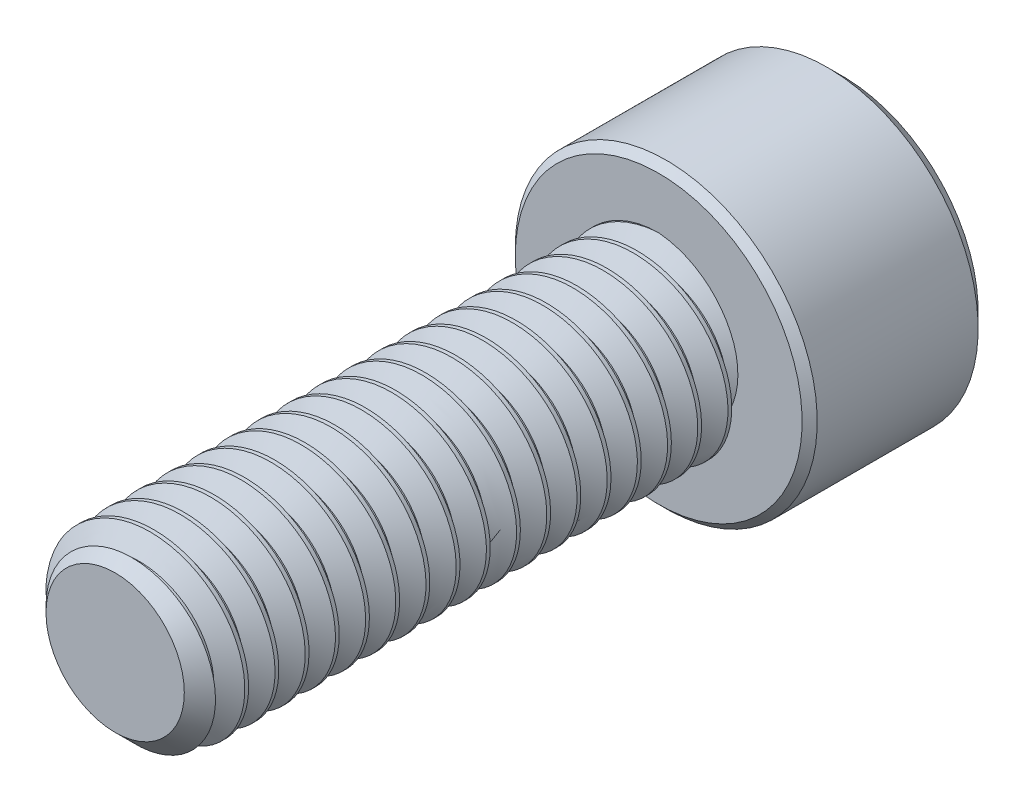
SolidWorks part; units mm, degrees
ref_plane "Front Plane" through (0, 0, 0) normal (0, 0, 1) x (1, 0, 0)
ref_plane "Top Plane" through (0, 0, 0) normal (0, 1, 0) x (1, 0, 0)
ref_plane "Right Plane" through (0, 0, 0) normal (1, 0, 0) x (0, 0, -1)
sketch "Sketch0" plane through (0, 0, 0) normal (1, 0, 0) x (0, 0, -1)
  line L0 (0, 0) -> (14.2875, 0) construction
  point P2 (19.1135, 0)
  point P4 (0, 0)
  dimension "D1" = 14.2875
  dimension "D2" = 4.826
  dimension "Min Thread" = 0
sketch "Sketch1" plane through (0, 0, 0) normal (0, 0, 1) x (1, 0, 0)
  circle A0 centre (0, 0) radius 2.413
  dimension "OD" = 4.826
extrude "Extrude1" add sketch "Sketch1" against normal blind 14.2875
sketch "Sketch2" plane through (0, 0, 0) normal (0, 0, 1) x (1, 0, 0)
  circle A0 centre (0, 0) radius 2.413 construction
  circle A1 centre (0, 0) radius 2.413
curve "Helix/Spiral1" pitch 0.7937 height 15.0812 turns 19 parameters "pitch"=0.7937
chamfer "Chamfer3" distance 0.5953 angle 45 1 edges at (2.413, 0, 0)
sketch "Sketch3" plane through (0, 0, 0) normal (1, 0, 0) x (0, 0, -1)
  line L0 (-0.6945, 2.413) -> (-0.3969, 1.8974)
  line L1 (-0.3969, 1.8974) -> (-0.2977, 1.8974)
  line L2 (-0.2977, 1.8974) -> (0, 2.413)
  line L3 (-0.6945, 2.413) -> (0, 2.413)
  line L4 (-0.3473, 2.413) -> (-0.3473, 1.8974) construction
  line L5 (-0.5457, 2.1552) -> (-0.1488, 2.1552) construction
  line L6 (0, 2.413) -> (0, -2.413) construction
  dimension "D1" = 0.0992
  dimension "D2" = 0.3969
  dimension "D3" = 60
sweep "Cut-Sweep1" cut profiles "Sketch3" path "Helix/Spiral1"
sketch "Sketch5" plane through (0, 0, 0) normal (1, 0, 0) x (0, 0, -1)
  line L0 (14.2875, -1.9083) -> (14.2875, 1.7217) construction
  line L1 (14.2875, 2.413) -> (0, 2.413)
  line L2 (14.2875, 2.413) -> (14.2875, 0)
  line L3 (14.2875, 0) -> (-0.8783, 0)
  line L4 (0, 0) -> (14.2875, 0) construction
  line L5 (0, 2.413) -> (-0.8783, 0)
  line L6 (0, 0) -> (16.8275, 0) construction
  dimension "D1" = 70
  dimension "D3" = 2.54
revolve "partially thread" [suppressed] add sketch "Sketch5" angle 360 about L6
sketch "Sketch6" plane through (0, 0, -14.2875) normal (0, 0, -1) x (-1, 0, 0)
  circle A0 centre (0, 0) radius 3.9688
  dimension "head dia" = 7.9375
extrude "Extrude2" add sketch "Sketch6" along normal blind 4.826
sketch "Sketch7" plane through (0, 0, -19.1135) normal (0, 0, -1) x (-1, 0, 0)
  line L1 (0, 2.2914) -> (-1.9844, 1.1457)
  line L2 (-1.9844, 1.1457) -> (-1.9844, -1.1457)
  line L3 (-1.9844, -1.1457) -> (0, -2.2914)
  line L4 (0, -2.2914) -> (1.9844, -1.1457)
  line L5 (1.9844, -1.1457) -> (1.9844, 1.1457)
  line L6 (1.9844, 1.1457) -> (0, 2.2914)
  circle A0 centre (0, 0) radius 1.9844 construction
  dimension "hex dia" = 3.9688
extrude "Cut-Extrude1" cut sketch "Sketch7" against normal blind 2.9766
sketch "Sketch8" plane through (0, 0, -19.1135) normal (0, 0, -1) x (-1, 0, 0)
  circle A0 centre (0, 0) radius 2.2914
extrude "Cut-Extrude2" cut sketch "Sketch8" against normal through all draft 45
chamfer "Chamfer1" distance 0.3969 angle 45 1 edges at (-3.9688, 0, -19.1135)
chamfer "Chamfer2" distance 0.1984 angle 45 1 edges at (-3.9688, 0, -14.2875)
sketch "Sketch9" plane through (0, 0, 0) normal (1, 0, 0) x (0, 0, -1)
  line L0 (0, 2.413) -> (0, -2.413) construction
  line L1 (1.9844, 2.413) -> (1.9844, -2.413) construction
  line L2 (19.1135, 3.9688) -> (19.1135, -3.9688) construction
  line L3 (14.2875, 3.9688) -> (14.2875, -3.9688) construction
  line L4 (14.2875, 3.7703) -> (14.2875, -3.7703) construction
  line L5 (19.1135, -3.5719) -> (19.1135, 3.5719) construction
  line L6 (14.2875, -3.9688) -> (14.2875, 3.9688) construction
  line L7 (0, 1.8177) -> (0, -1.8177) construction
  line L8 (-0.6945, 2.413) -> (0, 2.413) construction
  line L9 (1.9844, 0) -> (0, 0) construction
  dimension "D1" = 1.9844
equation "\"D3@Helix/Spiral1\" = \"screw length@Extrude1\"+\"pitch@Helix/Spiral1\""
equation "\"D1@Sketch3\" = \"pitch@Helix/Spiral1\"*.125"
equation "\"D2@Sketch3\" = \"pitch@Helix/Spiral1\"*.5"
equation "\"D1@Cut-Extrude1\" = \"hex dia@Sketch7\"*.75"
equation "\"D1@Chamfer1\" = \"head dia@Sketch6\"*.05"
equation "\"D1@Sketch9\" = \"pitch@Helix/Spiral1\"*2.50"
equation "\"D1@Chamfer2\" = \"D1@Chamfer1\"/2"
equation "\"D1@Chamfer3\" = \"pitch@Helix/Spiral1\"*.750"
equation "\"D1@Sketch0\" = \"screw length@Extrude1\""
equation "\"D2@Sketch0\" = \"head depth@Extrude2\""
